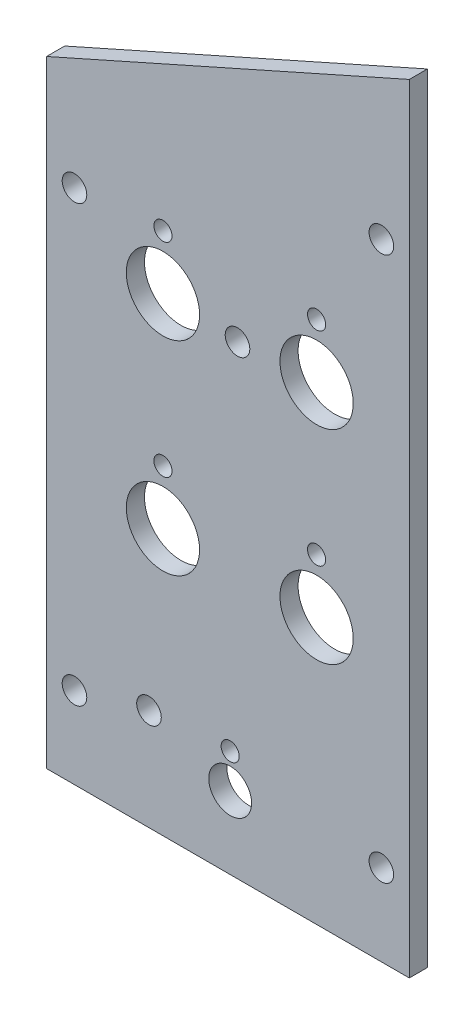
SolidWorks part; units mm, degrees
material "PET"
ref_plane "Front Plane" through (0, 0, 0) normal (0, 0, 1) x (1, 0, 0)
ref_plane "Top Plane" through (0, 0, 0) normal (0, 1, 0) x (1, 0, 0)
ref_plane "Right Plane" through (0, 0, 0) normal (1, 0, 0) x (0, 0, -1)
sketch "Sketch1" plane through (0, 0, 0) normal (0, 0, 1) x (1, 0, 0)
  line L4 (0, 107.95) -> (0, 0)
  line L5 (0, 0) -> (63.5, 0)
  line L6 (63.5, 0) -> (63.5, 136.2202)
  line L7 (63.5, 136.2202) -> (0, 107.95)
  line L8 (0, 107.95) -> (0, 0)
  line L9 (0, 0) -> (63.5, 0)
  line L10 (63.5, 0) -> (63.5, 136.2202)
  line L11 (63.5, 136.2202) -> (0, 107.95)
  dimension "D1" = 0
extrude "Boss-Extrude1" add sketch "Sketch1" against normal blind 3.175
hole_wizard "#6 Clearance Hole1" positions "Sketch4" profile "Sketch3" hole size "#6" standard "ANSI Inch" end condition through all
sketch "Sketch4" plane through (0, 0, 0) normal (0, 0, 1) x (1, 0, 0)
  point P0 (58.6105, 14.2875)
  point P3 (4.8895, 14.2875)
  point P6 (4.8895, 90.4875)
  point P9 (58.6105, 109.5375)
sketch "Sketch3" plane through (58.6105, 14.2875, 0) normal (1, 0, 0) x (0, -1, 0)
  line L0 (0, 0) -> (0, 3.175)
  line L1 (0, 3.175) -> (2.1526, 3.175)
  line L2 (2.1526, 3.175) -> (2.1526, 0)
  line L5 (2.1526, 0) -> (0, 0)
  line L11 (0, -6.35) -> (0, 107.95) construction
  dimension "Thru Hole Dia." = 4.3053
  dimension "Thru Hole Depth" = 3.175
sketch "Sketch8" plane through (0, 0, 0) normal (0, 0, 1) x (1, 0, 0)
  line L0 (0, 0) -> (63.5, 0) construction
  line L1 (20.3732, 91.7104) -> (20.3732, 82.1854) construction
  line L2 (20.3732, 56.073) -> (20.3732, 46.548) construction
  line L3 (47.2705, 46.548) -> (47.2705, 56.073) construction
  line L4 (32.1439, 18.7) -> (32.1439, 12.7) construction
  line L5 (81.6444, 34.0155) -> (81.6444, 24.4905) construction
  line L6 (47.2705, 82.1854) -> (47.2705, 91.7104) construction
  line L7 (0, 107.95) -> (0, 0) construction
  circle A1 centre (20.3732, 91.7104) radius 1.5875
  circle A2 centre (47.2705, 91.7104) radius 1.5875
  circle A3 centre (47.2705, 56.073) radius 1.5875
  circle A4 centre (32.1439, 12.7) radius 3.75
  circle A5 centre (20.3732, 56.073) radius 1.5875
  circle A6 centre (32.1439, 18.7) radius 1.5875
  circle A10 centre (47.2705, 46.548) radius 6.4135
  circle A12 centre (47.2705, 82.1854) radius 6.4135
  circle A15 centre (20.3732, 82.1854) radius 6.4135
  circle A17 centre (20.3732, 46.548) radius 6.4135
  circle A18 centre (81.6444, 34.0155) radius 1.651 construction
  circle A19 centre (81.6444, 24.4905) radius 6.4135 construction
  dimension "D2" = 26.8973
  dimension "D3" = 12.827
  dimension "D9" = 3.175
  dimension "D10" = 3.175
  dimension "D11" = 3.175
  dimension "D12" = 3.175
  dimension "D13" = 3.175
  dimension "D14" = 7.5
  dimension "D1" = 9.525
  dimension "D4" = 35.6374
  dimension "D5" = 33.848
  dimension "D6" = 15.1266
  dimension "D7" = 12.7
  dimension "D8" = 32.1439
  dimension "D15" = 6
extrude "Cut-Extrude1" cut sketch "Sketch8" against normal through all
hole_wizard "#6 Clearance Hole2" positions "Sketch9" profile "Sketch10" hole size "#6" standard "ANSI Inch" end condition through all
sketch "Sketch9" plane through (31.75, 0, 4.765) normal (0, 0, 1) x (1, 0, 0)
  point P0 (1.6763, 81.3834)
  point P2 (-13.8187, 17.7712)
sketch "Sketch10" plane through (33.4263, 81.3834, 4.765) normal (1, 0, 0) x (0, -1, 0)
  line L0 (0, 0) -> (0, 7.94)
  line L1 (0, 7.94) -> (2.1526, 7.94)
  line L2 (2.1526, 7.94) -> (2.1526, 0)
  line L3 (2.1526, 0) -> (0, 0)
  line L4 (0, -6.35) -> (0, 107.95) construction
  dimension "Thru Hole Dia." = 4.3053
  dimension "Thru Hole Depth" = 7.94
